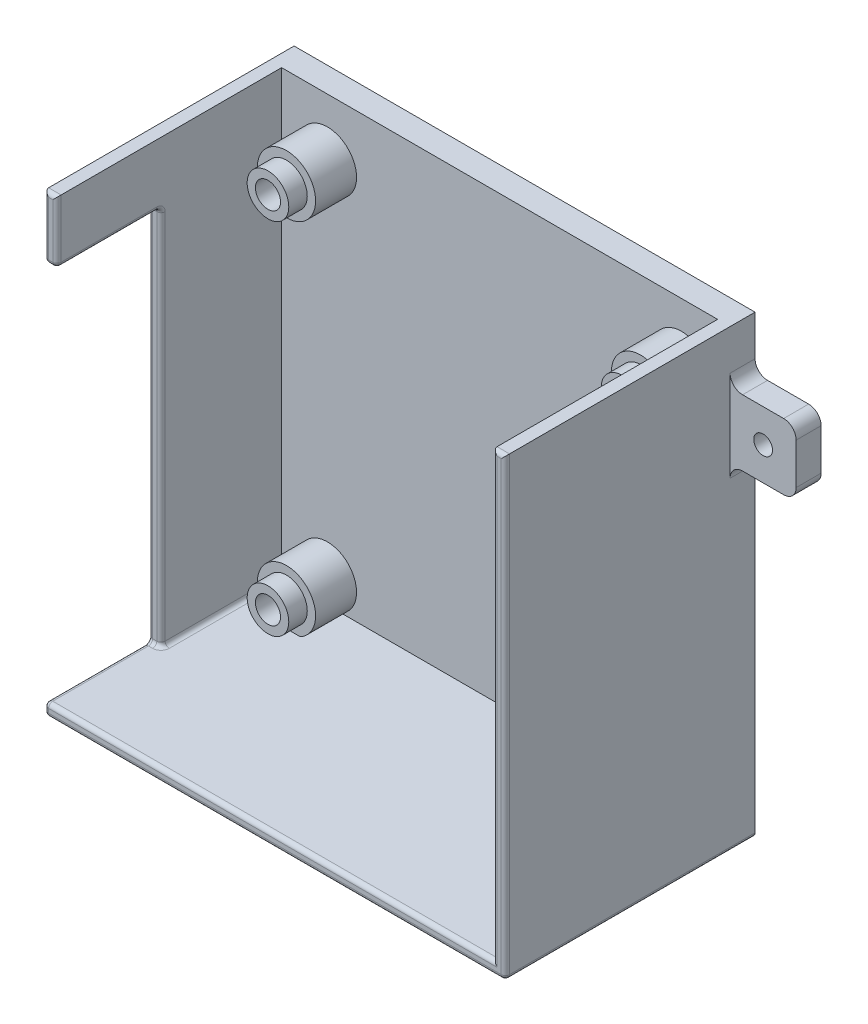
SolidWorks part; units mm, degrees
material "ABS"
ref_plane "X-Y Datum" through (0, 0, 0) normal (0, 0, 1) x (1, 0, 0)
ref_plane "X-Z Datum" through (0, 0, 0) normal (0, 1, 0) x (1, 0, 0)
ref_plane "Y-Z Datum" through (0, 0, 0) normal (1, 0, 0) x (0, 0, -1)
sketch "Sketch1" plane through (0, 0, 0) normal (0, 0, 1) x (1, 0, 0)
  line L1 (-52.3875, 53.1812) -> (52.3875, 53.1812)
  line L2 (-52.3875, 53.1812) -> (-52.3875, -53.1812)
  line L3 (-52.3875, -53.1812) -> (52.3875, -53.1812)
  line L4 (52.3875, 53.1812) -> (52.3875, -53.1812)
  line L5 (-52.3875, 53.1812) -> (52.3875, -53.1812) construction
  line L6 (-52.3875, -53.1812) -> (52.3875, 53.1812) construction
  point P0 (0, 0)
  dimension "D1" = 104.775
  dimension "D2" = 106.3625
extrude "Boss-Extrude1" add sketch "Sketch1" along normal blind 6
sketch "Sketch2" plane through (0, 0, 0) normal (0, 0, 1) x (1, 0, 0)
  line L1 (-55.3875, -53.1812) -> (-55.3875, -56.1812)
  line L2 (-55.3875, 53.1812) -> (-55.3875, -53.1812)
  line L4 (55.3875, 53.1812) -> (52.3875, 53.1812)
  line L5 (55.3875, -56.1812) -> (55.3875, 53.1812)
  line L6 (-52.3875, -56.1812) -> (55.3875, -56.1812)
  line L7 (55.3875, -56.1812) -> (55.3875, 53.1812)
  line L8 (-52.3875, -56.1812) -> (55.3875, -56.1812)
  line L9 (52.3875, -53.1812) -> (52.3875, 53.1812) construction
  line L10 (-52.3875, -53.1812) -> (52.3875, -53.1812) construction
  line L11 (52.3875, -53.1812) -> (52.3875, 53.1812)
  line L12 (-52.3875, -53.1812) -> (52.3875, -53.1812)
  line L13 (-55.3875, 53.1812) -> (-55.3875, -53.1812)
  line L14 (-55.3875, -56.1812) -> (-52.3875, -56.1812)
  line L15 (-55.3875, 53.1812) -> (-52.3875, 53.1812)
  line L16 (-52.3875, 53.1812) -> (-52.3875, -53.1812) construction
  line L17 (-52.3875, 53.1812) -> (-52.3875, -53.1812)
  dimension "D1" = 3
  dimension "D2" = 3
extrude "Boss-Extrude2" add sketch "Sketch2" along normal blind 35
sketch "Sketch3" plane through (0, 0, 6) normal (0, 0, 1) x (1, 0, 0)
  circle A0 centre (-41.382, 39.351) radius 3.025
  circle A1 centre (43.708, 39.351) radius 3.025
  circle A2 centre (43.708, -47.009) radius 3.025
  circle A3 centre (-41.382, -47.009) radius 3.025
  circle A4 centre (43.708, 39.351) radius 5
  circle A5 centre (-41.382, 39.351) radius 5
  circle A6 centre (-41.382, -47.009) radius 5
  circle A7 centre (43.708, -47.009) radius 5
  point P0 (-41.382, 39.351)
  point P1 (-41.382, -47.009)
  point P3 (43.708, -47.009)
  point P5 (43.708, 39.351)
  dimension "D1" = 6.05
  dimension "D2" = 10
extrude "Boss-Extrude3" add sketch "Sketch3" along normal blind 14.2875
sketch "Sketch4" plane through (0, 0, 6) normal (0, 0, 1) x (1, 0, 0)
  circle A0 centre (43.708, 39.351) radius 7
  circle A1 centre (-41.382, 39.351) radius 7
  circle A2 centre (-41.382, -47.009) radius 7
  circle A3 centre (43.708, -47.009) radius 7
  circle A5 centre (-41.382, -47.009) radius 3.025
  circle A6 centre (-41.382, -47.009) radius 3.025
  circle A7 centre (43.708, -47.009) radius 3.025
  circle A8 centre (43.708, -47.009) radius 3.025
  circle A9 centre (43.708, 39.351) radius 3.025
  circle A10 centre (43.708, 39.351) radius 3.025
  circle A11 centre (-41.382, 39.351) radius 3.025
  circle A12 centre (-41.382, 39.351) radius 3.025
  dimension "D1" = 14
  dimension "D2" = 0
  dimension "D3" = 0
  dimension "D4" = 0
  dimension "D5" = 0
extrude "Boss-Extrude4" add sketch "Sketch4" along normal blind 9.8425
sketch "Sketch6" plane through (0, 0, 0) normal (0, 0, 1) x (1, 0, 0)
  line L0 (-71.2675, -40.3012) -> (-55.3875, -56.1812) construction
  line L5 (55.3875, -56.1812) -> (55.3875, 53.1812) construction
  line L6 (55.3875, 40.4812) -> (71.2625, 40.4812)
  line L7 (55.3875, 40.4812) -> (55.3875, 24.6062)
  line L8 (55.3875, 24.6062) -> (71.2625, 24.6062)
  line L9 (71.2625, 40.4812) -> (71.2625, 24.6062)
  line L10 (55.3875, 24.6062) -> (71.2625, 40.4812)
  line L11 (55.3875, 53.1812) -> (52.3875, 53.1812) construction
  line L13 (-55.3875, -56.1812) -> (-71.2675, -56.1812)
  line L14 (-55.3875, -56.1812) -> (-55.3875, -40.3012)
  line L15 (-55.3875, -40.3012) -> (-71.2675, -40.3012)
  line L17 (-71.2675, -56.1812) -> (-71.2675, -40.3012)
  circle A1 centre (63.325, 32.5437) radius 2 construction
  circle A2 centre (-63.3275, -48.2413) radius 2 construction
  dimension "D1" = 15.88
  dimension "D6" = 4
  dimension "D2" = 4
  dimension "D4" = 15.875
  dimension "D5" = 15.875
  dimension "D7" = 12.7
extrude "Boss-Extrude5" add sketch "Sketch6" along normal blind 6 contours L14 L15 | L17 L13 | L10 L8 L9 | L7 L10 L6 region at (60.6792, 35.1896, 0) region at (65.9708, 29.8979, 0) region at (-63.3275, -48.2412, 0)
hole_wizard "M4 Clearance Hole1" positions "Sketch7" profile "Sketch8" hole size "M4" standard "ANSI Metric" end condition through all
sketch "Sketch7" plane through (0, 0, 6) normal (0, 0, 1) x (1, 0, 0)
  point P0 (63.325, 32.5437)
  point P8 (-63.3275, -48.2413)
sketch "Sketch8" plane through (63.325, 32.5437, 6) normal (1, 0, 0) x (0, -1, 0)
  line L0 (0, 0) -> (0, 6)
  line L1 (0, 6) -> (2.25, 6)
  line L2 (2.25, 6) -> (2.25, 0)
  line L5 (2.25, 0) -> (0, 0)
  line L11 (0, -6.35) -> (0, 107.95) construction
  dimension "Thru Hole Dia." = 4.5
  dimension "Thru Hole Depth" = 6
fillet "Fillet2" radius 3 6 edges at (71.2625, 24.6062, 3) (71.2625, 40.4812, 3) (55.3875, 40.4812, 3) (55.3875, 24.6062, 3) (-71.2675, -56.1812, 3) (-71.2675, -40.3012, 3)
sketch "Sketch9" plane through (0, 0, 35) normal (0, 0, 1) x (1, 0, 0)
  line L0 (-52.3875, 38.1812) -> (-55.3875, 38.1812)
  line L1 (-52.3875, -53.1812) -> (-55.3875, -53.1812)
  line L8 (-52.3875, -53.1812) -> (-52.3875, 53.1812)
  line L9 (-52.3875, 53.1812) -> (-55.3875, 53.1812)
  line L10 (-55.3875, 53.1812) -> (-55.3875, -56.1812)
  line L11 (-55.3875, -56.1812) -> (55.3875, -56.1812)
  line L12 (55.3875, -56.1812) -> (55.3875, 53.1812)
  line L13 (55.3875, 53.1812) -> (52.3875, 53.1812)
  line L14 (52.3875, 53.1812) -> (52.3875, -53.1812)
  line L15 (52.3875, -53.1812) -> (-52.3875, -53.1812)
  line L16 (-52.3875, -53.1812) -> (-52.3875, 53.1812)
  line L17 (-52.3875, 53.1812) -> (-55.3875, 53.1812)
  line L18 (-55.3875, 53.1812) -> (-55.3875, -56.1812)
  line L19 (-55.3875, -56.1812) -> (55.3875, -56.1812)
  line L20 (55.3875, -56.1812) -> (55.3875, 53.1812)
  line L21 (55.3875, 53.1812) -> (52.3875, 53.1812)
  line L22 (52.3875, 53.1812) -> (52.3875, -53.1812)
  line L23 (52.3875, -53.1812) -> (-52.3875, -53.1812)
  line M10 (-52.3875, -53.1812) -> (-52.3875, 53.1812)
  line M11 (-52.3875, 53.1812) -> (-55.3875, 53.1812)
  line M12 (-55.3875, 53.1812) -> (-55.3875, -56.1812)
  line M13 (-55.3875, -56.1812) -> (55.3875, -56.1812)
  line M14 (55.3875, -56.1812) -> (55.3875, 53.1812)
  line M15 (55.3875, 53.1812) -> (52.3875, 53.1812)
  line M16 (52.3875, 53.1812) -> (52.3875, -53.1812)
  line M17 (52.3875, -53.1812) -> (-52.3875, -53.1812)
  dimension "D2" = 15
  dimension "D1" = 0
extrude "Boss-Extrude6" add sketch "Sketch9" along normal blind 25 contours L1 M17 M12 M13 M14 M15 M16 | L0 M10 M11 M12 region at (-53.8875, 45.6812, 35) region at (0, -54.7379, 35)
fillet "Fillet3" radius 1 20 edges at (-53.8875, -53.1812, 35) (55.3875, -56.1812, 30) (-55.3875, -7.5, 35) (-52.3875, -7.5, 35) (-52.3875, -53.1812, 20.5) (-55.3875, -56.1812, 33) (-52.3875, 38.1812, 47.5) (-55.3875, -53.1812, 47.5) (-55.3875, 38.1812, 47.5) (-53.8875, 38.1812, 35) (52.3875, 0, 60) (53.8875, 53.1812, 60) (55.3875, -1.5, 60) (0, -56.1812, 60) (-55.3875, -54.6812, 60) (-1.5, -53.1812, 60) (-55.3875, 45.6812, 60) (-53.8875, 53.1812, 60) (-52.3875, 45.6812, 60) (-53.8875, 38.1812, 60)
